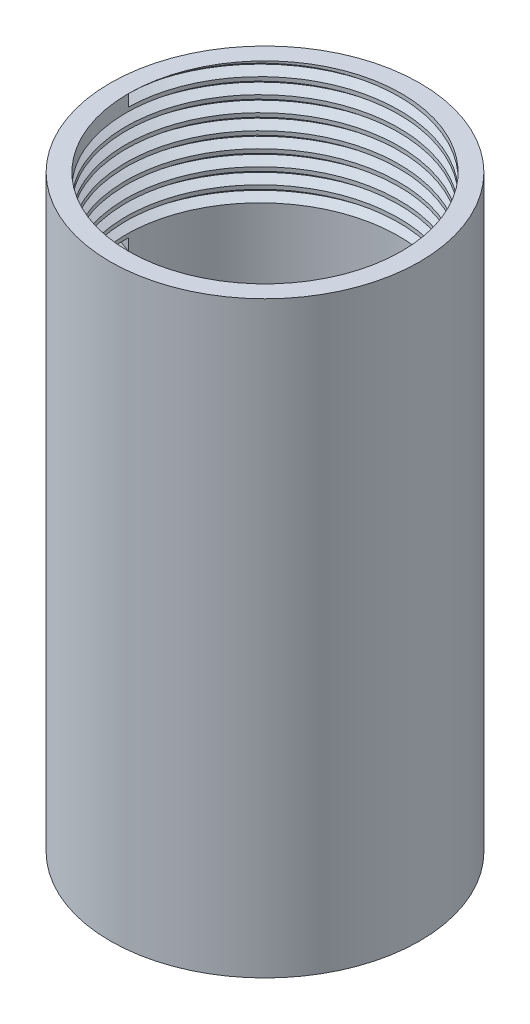
SolidWorks part; units mm, degrees
ref_plane "Front Plane" through (0, 0, 0) normal (0, 0, 1) x (1, 0, 0)
ref_plane "Top Plane" through (0, 0, 0) normal (0, 1, 0) x (1, 0, 0)
ref_plane "Right Plane" through (0, 0, 0) normal (1, 0, 0) x (0, 0, -1)
sketch "Sketch1" plane through (0, 0, 0) normal (0, 1, 0) x (1, 0, 0)
  circle A0 centre (0, 0) radius 5.95
  dimension "D1" = 11.9
extrude "Boss-Extrude1" add sketch "Sketch1" along normal blind 22.61
sketch "Sketch2" plane through (0, 22.61, 0) normal (0, 1, 0) x (1, 0, 0)
  circle A0 centre (0, 0) radius 5.25
  dimension "D1" = 10.5
extrude "Cut-Extrude1" cut sketch "Sketch2" against normal blind 21.93
sketch "Sketch3" plane through (0, 0.68, 0) normal (0, 1, 0) x (1, 0, 0)
  circle A0 centre (0, 0) radius 1.71
  dimension "D1" = 3.42
extrude "Cut-Extrude2" cut sketch "Sketch3" against normal through all
thread "Thread1" pitch 0.6 method cut profile "Thread Profile1" start angle 0, offset 0, length 4.8, pitch 0.6, diameter 10.5
ref_plane "Plane1" through (-5.25, 22.61, 0) normal (0, 0, 1) x (-1, 0, 0)
sketch "Thread Profile1" plane through (-5.25, 22.61, 0) normal (0, 0, 1) x (-1, 0, 0)
  line L0 (0, 0) -> (0, 0.6) construction
  line L1 (0, 0) -> (0.3248, 0.1875)
  line L2 (0.3248, 0.1875) -> (0.3248, 0.2625)
  line L3 (0.3248, 0.2625) -> (0, 0.45)
  line L4 (0.3248, 0.225) -> (0, 0.225) construction
  line L11 (0, 0) -> (0, 0.45)
  point P2 (0, 0)
  dimension "Pitch" = 0.6
  dimension "Profile_Angle" = 60
  dimension "Profile_Land" = 0.075
  dimension "Profile_Height" = 0.3248
